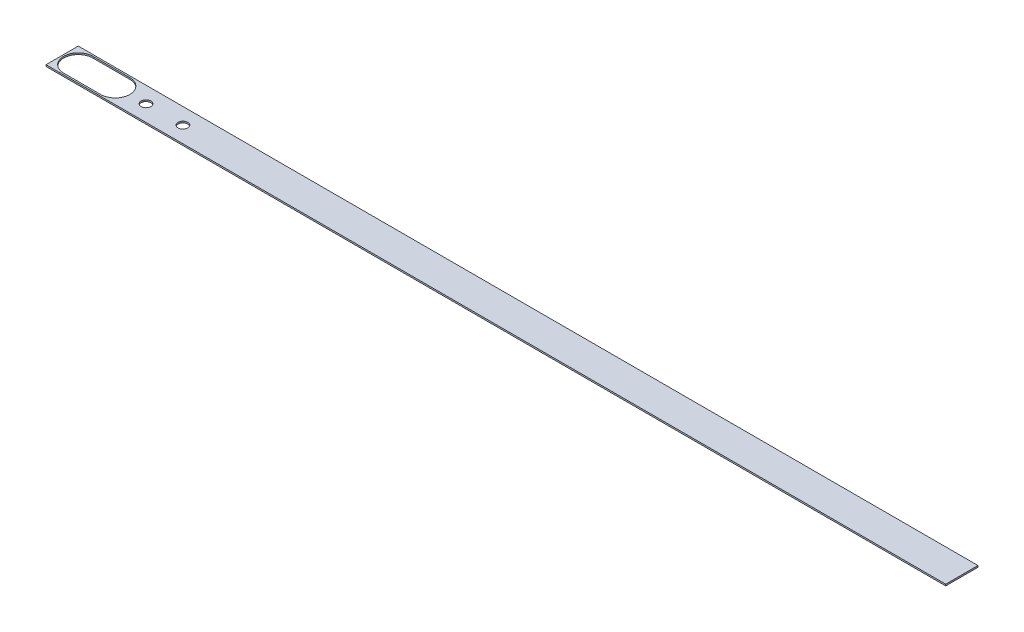
SolidWorks part; units mm, degrees
ref_plane "Front Plane" through (0, 0, 0) normal (0, 0, 1) x (1, 0, 0)
ref_plane "Top Plane" through (0, 0, 0) normal (0, 1, 0) x (1, 0, 0)
ref_plane "Right Plane" through (0, 0, 0) normal (1, 0, 0) x (0, 0, -1)
sketch "Sketch1" plane through (0, 0, 0) normal (0, 1, 0) x (1, 0, 0)
  line L1 (-462.5, 16.6) -> (462.5, 16.6)
  line L2 (-462.5, 16.6) -> (-462.5, -16.6)
  line L3 (-462.5, -16.6) -> (462.5, -16.6)
  line L4 (462.5, 16.6) -> (462.5, -16.6)
  line L5 (-462.5, 16.6) -> (462.5, -16.6) construction
  line L6 (-462.5, -16.6) -> (462.5, 16.6) construction
  point P0 (0, 0)
  dimension "D1" = 925
  dimension "D2" = 33.2
extrude "Boss-Extrude1" add sketch "Sketch1" against normal blind 1.6
sketch "Sketch2" plane through (0, 0, 0) normal (0, 1, 0) x (1, 0, 0)
  line L0 (-460.9, 16.6) -> (-460.9, -16.6) construction
  line L1 (462.5, 16.6) -> (-462.5, 16.6) construction
  line L2 (-462.5, -16.6) -> (462.5, -16.6) construction
  line L3 (-392.9, 16.6) -> (-392.9, -16.6) construction
  line L4 (-391.3, 16.6) -> (-391.3, -16.6) construction
  line L5 (-323.3, 16.6) -> (-323.3, -16.6) construction
  line L6 (-462.5, 16.6) -> (-462.5, -16.6) construction
  line L7 (-460.9, 0) -> (-323.3, 0) construction
  line L8 (-445.9, 15) -> (-407.9, 15)
  line L9 (-445.9, -15) -> (-407.9, -15)
  line L10 (-376.3, -15) -> (-338.3, -15) construction
  line L11 (-376.3, 15) -> (-338.3, 15) construction
  arc A0 (-445.9, 15) -> (-445.9, -15) centre (-445.9, 0) ccw
  arc A1 (-407.9, -15) -> (-407.9, 15) centre (-407.9, 0) ccw
  circle A2 centre (-376.3, 0) radius 5
  circle A3 centre (-338.3, 0) radius 5
  arc A4 (-338.3, -15) -> (-338.3, 15) centre (-338.3, 0) ccw construction
  arc A5 (-376.3, 15) -> (-376.3, -15) centre (-376.3, 0) ccw construction
  dimension "D5" = 15
  dimension "D8" = 10
  dimension "D1" = 1.6
  dimension "D2" = 68
  dimension "D3" = 1.6
  dimension "D4" = 68
  dimension "D6" = 15
  dimension "D7" = 15
  dimension "D9" = 137.6
  dimension "D10" = 2
extrude "Cut-Extrude1" cut sketch "Sketch2" against normal through all
curve "Curve1"
sketch "Sketch2<2>" plane through (0, 0, 0) normal (0, 1, 0) x (1, 0, 0) same geometry as "Sketch2"
